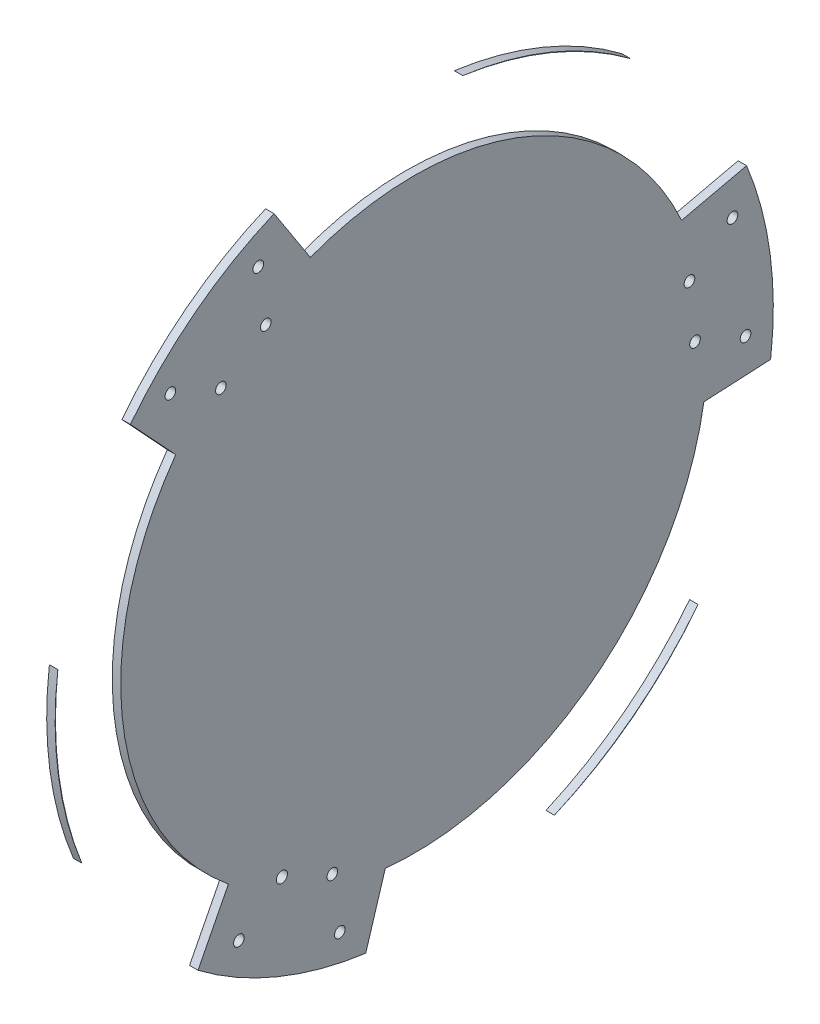
SolidWorks part; units mm, degrees
material "Oak"
ref_plane "Front Plane" through (0, 0, 0) normal (0, 0, 1) x (1, 0, 0)
ref_plane "Top Plane" through (0, 0, 0) normal (0, 1, 0) x (1, 0, 0)
ref_plane "Right Plane" through (0, 0, 0) normal (1, 0, 0) x (0, 0, -1)
sketch "Sketch2" plane through (0, 0, 0) normal (1, 0, 0) x (0, 0, -1)
  circle A0 centre (0, 0) radius 135
  dimension "D1" = 270
extrude "Boss-Extrude1" add sketch "Sketch2" along normal blind 3.18
sketch "Sketch4" plane through (3.18, 0, 0) normal (1, 0, 0) x (0, 0, -1)
  line L0 (78.0772, 110.1315) -> (-78.0772, -110.1315) construction
  circle A0 centre (0, 0) radius 135 construction
sketch "Sketch6" plane through (0, 0, 0) normal (-1, 0, 0) x (0, 0, 1)
  line L0 (-24.9024, -81.3474) -> (-52.6933, -124.2917)
  line L1 (14.603, -28.4478) -> (64.3096, -67.155) construction
  line L2 (-72.1816, -45.5152) -> (-106.723, -82.6753)
  line L3 (-82.9001, -19.1075) -> (-133.9864, -16.5121)
  line L4 (-75.5081, 39.7535) -> (-124.9604, 51.0872)
  line L5 (32.1134, -5.9614) -> (81.82, -44.6687) construction
  line L6 (-75.5081, 39.7535) -> (-82.9001, -19.1075)
  line L7 (-3.3265, 85.2687) -> (-18.2374, 133.7625)
  line L8 (-3.3265, 85.2687) -> (-57.9977, 62.2398)
  line L9 (-57.9977, 62.2398) -> (-81.2931, 107.7795)
  line L10 (72.1816, 45.5152) -> (106.723, 82.6753)
  line L11 (72.1816, 45.5152) -> (24.9024, 81.3474)
  line L12 (24.9024, 81.3474) -> (52.6933, 124.2917)
  line L13 (82.9001, 19.1075) -> (75.5081, -39.7535)
  line L14 (75.5081, -39.7535) -> (124.9604, -51.0872)
  line L15 (82.9001, 19.1075) -> (133.9864, 16.5121)
  line L16 (57.9977, -62.2398) -> (3.3265, -85.2687)
  line L17 (3.3265, -85.2687) -> (18.2374, -133.7625)
  line L18 (31.938, -1.5773) -> (90.3128, 22.1163) construction
  line L19 (57.9977, -62.2398) -> (81.2931, -107.7795)
  line L20 (-24.9024, -81.3474) -> (-72.1816, -45.5152)
  line L21 (21.2195, 24.8303) -> (79.5942, 48.5239) construction
  line L22 (-10.8939, 30.7917) -> (-2.2258, 93.1926) construction
  line L23 (17.335, 26.8704) -> (26.0031, 89.2713) construction
  line L24 (-72.1816, -45.5152) -> (-82.9001, -19.1075)
  line L25 (-24.9024, -81.3474) -> (3.3265, -85.2687)
  line L26 (57.9977, -62.2398) -> (75.5081, -39.7535)
  line L27 (82.9001, 19.1075) -> (72.1816, 45.5152)
  line L28 (-3.3265, 85.2687) -> (24.9024, 81.3474)
  line L29 (-75.5081, 39.7535) -> (-57.9977, 62.2398)
  line L33 (-32.1134, 5.9614) -> (-81.82, 44.6687) construction
  line L34 (-14.603, 28.4478) -> (-64.3096, 67.155) construction
  line L35 (-31.938, 1.5773) -> (-90.3128, -22.1163) construction
  line L36 (-21.2195, -24.8303) -> (-79.5942, -48.5239) construction
  line L37 (-17.335, -26.8704) -> (-26.0031, -89.2713) construction
  line L39 (10.8939, -30.7917) -> (2.2258, -93.1926) construction
  circle A0 centre (0, 0) radius 135 construction
  arc A2 (-81.2931, 107.7795) -> (-18.2374, 133.7625) centre (1.9664, -4.772) cw
  arc A3 (52.6933, 124.2917) -> (106.723, 82.6753) centre (-3.1495, -4.0889) cw
  arc A4 (133.9864, 16.5121) -> (124.9604, -51.0872) centre (-5.1159, 0.6831) cw
  arc A5 (81.2931, -107.7795) -> (18.2374, -133.7625) centre (-2.1152, 5.1332) cw
  arc A6 (-52.6933, -124.2917) -> (-106.723, -82.6753) centre (3.1495, 4.0889) cw
  arc A7 (-133.9864, -16.5121) -> (-124.9604, 51.0872) centre (5.1159, -0.6831) cw
  circle M4 centre (0, 0) radius 135
  dimension "D1" = 25
  dimension "D2" = 25
  dimension "D3" = 25
  dimension "D4" = 25
  dimension "D5" = 25
  dimension "D6" = 25
  dimension "D7" = 25
  dimension "D8" = 25
  dimension "D9" = 25
  dimension "D10" = 25
  dimension "D11" = 25
  dimension "D12" = 25
extrude "Cut-Extrude1" cut sketch "Sketch6" against normal through all contours L2 L24 L3 M4 | L0 L20 L2 M4 | L25 L0 L17 M4 | L26 L19 L14 M4 | L15 L13 L14 M4 | L27 L15 L10 M4 | L7 L28 L12 M4 | L9 L8 L7 M4 | L4 L29 L9 M4 region at (0, -111.3999, -14.7616) region at (0, -85.1242, -65.3595) region at (0, -42.916, -103.8559) region at (0, -68.4838, 89.0943) region at (0, 68.4838, -89.0943) region at (0, -14.0409, 106.3995) region at (0, 99.1651, -41.04) region at (0, 42.916, 103.8559) region at (0, 111.3999, 14.7616)
sketch "Sketch7" plane through (3.18, 0, 0) normal (1, 0, 0) x (0, 0, -1)
  line L0 (-100.2726, 34.0237) -> (-60.7833, 131.315) construction
  line L1 (-94.6312, 47.9225) -> (-105.9139, 20.125) construction
  line L2 (-60.7833, 131.315) -> (116.259, 59.4558) construction
  line L3 (50.4068, 86.1844) -> (22.6093, 97.467) construction
  line L4 (-100.2726, 34.0237) -> (-139.7619, -63.2676) construction
  line L5 (-139.7619, -63.2676) -> (54.8207, -142.2462) construction
  line L6 (54.8207, -142.2462) -> (133.7993, 52.3364) construction
  line L7 (133.7993, 52.3364) -> (116.259, 59.4558) construction
  line L8 (-56.3693, -97.1155) -> (-28.5718, -108.3982) construction
  line L9 (88.6687, -58.8536) -> (99.9513, -31.0561) construction
sketch "Sketch8" plane through (3.18, 0, 0) normal (1, 0, 0) x (0, 0, -1)
  circle A0 centre (0, 0) radius 110.3434
extrude "Boss-Extrude2" add sketch "Sketch8" against normal up to surface (3.18 mm away) up to face at (0, 0, 0)
sketch "Sketch9" plane through (0, 0, 0) normal (-1, 0, 0) x (0, 0, 1)
  circle A0 centre (30.7935, -101.7041) radius 2
  circle A1 centre (27.9729, -122.0092) radius 2
  circle A2 centre (65.9298, -105.7644) radius 2
  circle A3 centre (49.7555, -93.1692) radius 2.0926
  circle A4 centre (91.6766, 85.2299) radius 2
  circle A5 centre (72.6816, 77.52) radius 2
  circle A6 centre (55.8092, 89.6741) radius 2
  circle A7 centre (58.6298, 109.9791) radius 2
  circle A8 centre (-105.5646, 3.4951) radius 2
  circle A9 centre (-124.5596, -4.2147) radius 2
  circle A10 centre (-103.4751, 24.1841) radius 2
  circle A11 centre (-119.6495, 36.7793) radius 2
  point P36 (0, 0)
extrude "Cut-Extrude2" cut sketch "Sketch9" against normal through all contours A1 | A0 | A2 | A4 | A5 | A7 | A8 | A9 | A10 | A11 | A3 | A3 | A6 region at (0, -101.7041, 30.7935) region at (0, -122.0092, 27.9729) region at (0, -105.7644, 65.9298) region at (0, -93.1692, 49.7555) region at (0, 85.2299, 91.6766) region at (0, 77.52, 72.6816) region at (0, 109.9791, 58.6298) region at (0, 3.4951, -105.5646) region at (0, -4.2147, -124.5596) region at (0, 24.1841, -103.4751) region at (0, 36.7793, -119.6495)
